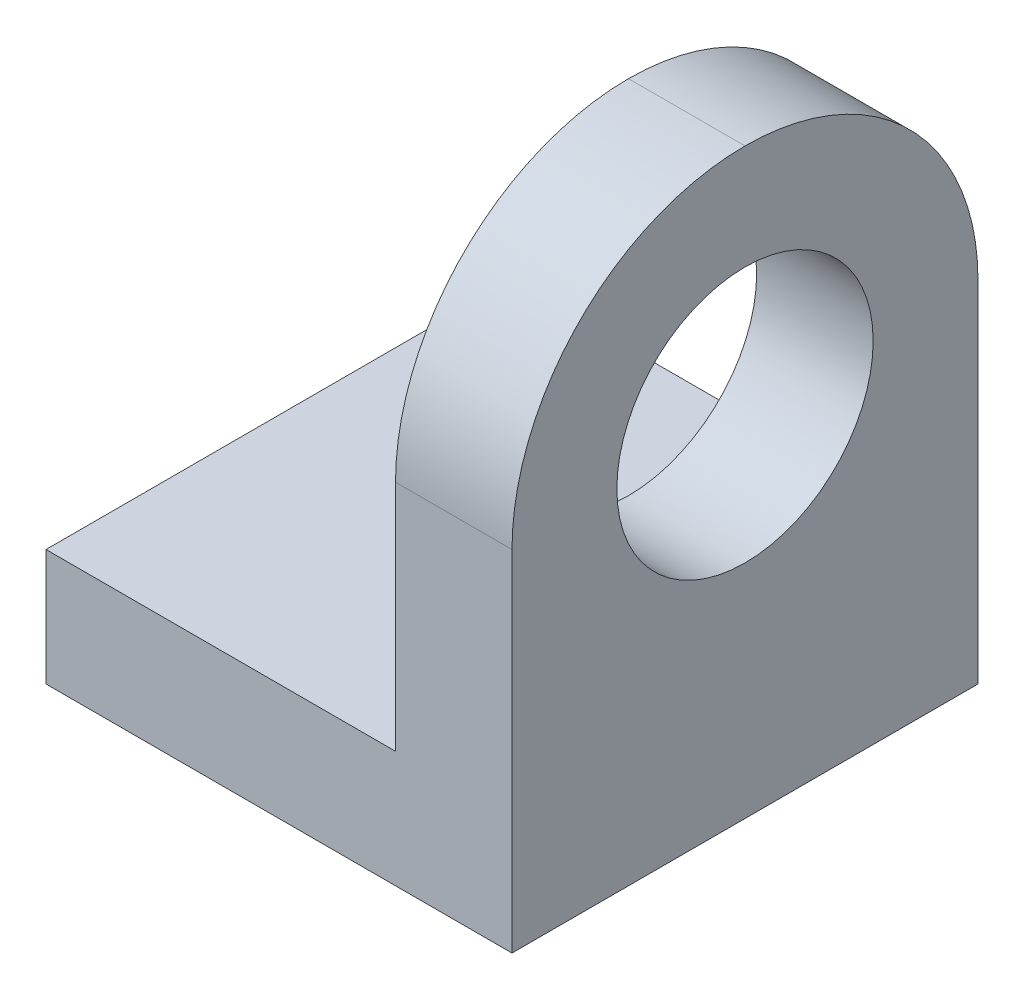
SolidWorks part; units mm, degrees
ref_plane "Front Plane" through (0, 0, 0) normal (0, 0, 1) x (1, 0, 0)
ref_plane "Top Plane" through (0, 0, 0) normal (0, 1, 0) x (1, 0, 0)
ref_plane "Right Plane" through (0, 0, 0) normal (1, 0, 0) x (0, 0, -1)
sketch "Sketch1" plane through (0, 0, 0) normal (0, 1, 0) x (1, 0, 0)
  line L1 (-10, 10) -> (10, 10)
  line L2 (-10, 10) -> (-10, -10)
  line L3 (-10, -10) -> (10, -10)
  line L4 (10, 10) -> (10, -10)
  line L5 (-10, 10) -> (10, -10) construction
  line L6 (-10, -10) -> (10, 10) construction
  point P0 (0, 0)
  dimension "D1" = 20
  dimension "D2" = 20
extrude "Boss-Extrude1" add sketch "Sketch1" along normal blind 5
sketch "Sketch2" plane through (0, 5, 0) normal (0, 1, 0) x (1, 0, 0)
  line L0 (-10, -10) -> (10, -10) construction
  line L1 (10, 10) -> (5, 10)
  line L2 (10, 10) -> (10, -10)
  line L3 (10, -10) -> (5, -10)
  line L4 (5, 10) -> (5, -10)
  dimension "D1" = 5
extrude "Boss-Extrude2" add sketch "Sketch2" along normal blind 20
sketch "Sketch3" plane through (10, 0, 0) normal (1, 0, 0) x (0, 0, -1)
  line L0 (-10, 25) -> (10, 25) construction
  circle A0 centre (0, 15) radius 5.5
  dimension "D1" = 11
  dimension "D2" = 10
extrude "Cut-Extrude1" cut sketch "Sketch3" against normal through all
fillet "Fillet1" radius 10 2 edges at (7.5, 25, -10) (7.5, 25, 10)
